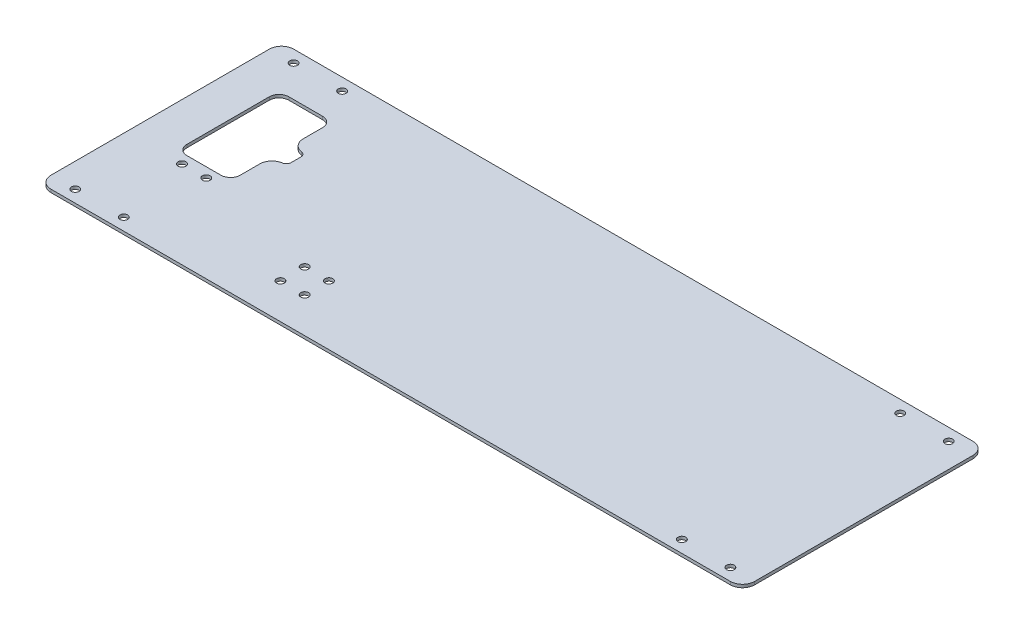
SolidWorks part; units mm, degrees
ref_plane "Front Plane" through (0, 0, 0) normal (0, 0, 1) x (1, 0, 0)
ref_plane "Top Plane" through (0, 0, 0) normal (0, 1, 0) x (1, 0, 0)
ref_plane "Right Plane" through (0, 0, 0) normal (1, 0, 0) x (0, 0, -1)
sketch "Sketch1" plane through (0, 0, 0) normal (0, 1, 0) x (1, 0, 0)
  line L0 (128.27, 0) -> (-128.27, 0) construction
  line L1 (184.15, 63.5) -> (-184.15, 63.5)
  line L2 (184.15, 63.5) -> (184.15, -63.5)
  line L3 (184.15, -63.5) -> (-184.15, -63.5)
  line L4 (-184.15, 63.5) -> (-184.15, -63.5)
  line L5 (184.15, 63.5) -> (-184.15, -63.5) construction
  line L6 (184.15, -63.5) -> (-184.15, 63.5) construction
  line L7 (-128.27, 0) -> (-128.27, 31.75) construction
  line L8 (-128.27, 31.75) -> (-134.62, 31.75) construction
  line L9 (-128.27, -6.35) -> (-134.62, -6.35) construction
  line L12 (-162.56, -12.7) -> (-162.56, 40.64)
  line L15 (-134.62, -12.7) -> (-162.56, -12.7)
  line L17 (-134.62, 40.64) -> (-162.56, 40.64)
  line L18 (0, 63.5) -> (0, -63.5) construction
  line L19 (-134.62, 40.64) -> (-134.62, -12.7)
  line L20 (-162.56, 31.75) -> (-168.91, 31.75) construction
  line L21 (-76.2, -45.0215) -> (-76.2, -32.3215) construction
  line L22 (-63.5, -45.0215) -> (-76.2, -45.0215) construction
  line L23 (-162.56, -3.81) -> (-168.91, -3.81) construction
  line L25 (128.27, 31.75) -> (128.27, -6.35) construction
  line L26 (-76.2, -32.3215) -> (-63.5, -32.3215) construction
  line L30 (-63.5, -32.3215) -> (-63.5, -45.0215) construction
  line L31 (184.15, -17.78) -> (154.94, -17.78) construction
  line L32 (146.05, 57.15) -> (184.15, 57.15) construction
  line L33 (154.94, -17.78) -> (142.24, -17.78) construction
  line L34 (146.05, -57.15) -> (184.15, -57.15) construction
  line L35 (-146.05, -57.15) -> (-184.15, -57.15) construction
  line L36 (-146.05, 57.15) -> (-184.15, 57.15) construction
  line L37 (-128.27, 0) -> (-128.27, -6.35) construction
  line L38 (-184.15, -17.78) -> (-154.94, -17.78) construction
  line L39 (-154.94, -17.78) -> (-142.24, -17.78) construction
  line L40 (-134.62, 19.05) -> (-127, 19.05)
  line L41 (-127, 19.05) -> (-127, 8.89)
  line L42 (-127, 8.89) -> (-134.62, 8.89)
  circle A0 centre (-128.27, 31.75) radius 2.032 construction
  circle A1 centre (-128.27, -6.35) radius 2.032 construction
  circle A2 centre (-168.91, 31.75) radius 2.032 construction
  circle A3 centre (-168.91, -3.81) radius 2.032 construction
  circle A4 centre (168.91, 31.75) radius 2.032 construction
  circle A5 centre (128.27, 31.75) radius 2.032 construction
  circle A6 centre (128.27, -6.35) radius 2.032 construction
  circle A7 centre (168.91, -3.81) radius 2.032 construction
  circle A8 centre (171.45, -57.15) radius 2.032
  circle A9 centre (146.05, -57.15) radius 2.032
  circle A10 centre (171.45, 57.15) radius 2.032
  circle A11 centre (146.05, 57.15) radius 2.032
  circle A12 centre (-146.05, -57.15) radius 2.032
  circle A13 centre (-171.45, -57.15) radius 2.032
  circle A14 centre (-146.05, 57.15) radius 2.032
  circle A15 centre (-171.45, 57.15) radius 2.032
  circle A16 centre (142.24, -17.78) radius 2.032 construction
  circle A17 centre (154.94, -17.78) radius 2.032 construction
  circle A18 centre (-154.94, -17.78) radius 2.032
  circle A19 centre (-142.24, -17.78) radius 2.032
  circle A20 centre (-76.2, -45.0215) radius 2.032
  circle A21 centre (-63.5, -45.0215) radius 2.032
  circle A22 centre (-76.2, -32.3215) radius 2.032
  circle A23 centre (-63.5, -32.3215) radius 2.032
  point P0 (0, 0)
  point P11 (-128.27, 0)
  point P13 (-134.62, 31.75)
  point P17 (-134.62, -6.35)
  point P37 (0, 0)
  point P50 (171.45, 57.15)
  point P51 (146.05, 57.15)
  point P56 (171.45, -57.15)
  point P57 (146.05, -57.15)
  point P84 (-130.81, 19.05)
  point P87 (130.81, 19.05)
  dimension "D5" = 4.064
  dimension "D6" = 8.89
  dimension "D18" = 4.064
  dimension "D1" = 368.3
  dimension "D2" = 127
  dimension "D3" = 128.27
  dimension "D4" = 38.1
  dimension "D7" = 6.35
  dimension "D8" = 27.94
  dimension "D9" = 53.34
  dimension "D10" = 8.89
  dimension "D11" = 6.35
  dimension "D12" = 8.89
  dimension "D13" = 15.24
  dimension "D14" = 12.7
  dimension "D15" = 38.1
  dimension "D16" = 12.7
  dimension "D17" = 38.1
  dimension "D19" = 31.75
  dimension "D20" = 6.35
  dimension "D21" = 6.35
  dimension "D22" = 5.08
  dimension "D23" = 29.21
  dimension "D24" = 12.7
  dimension "D25" = 107.95
  dimension "D26" = 12.7
  dimension "D27" = 7.62
  dimension "D28" = 10.16
  dimension "D29" = 21.59
  dimension "D30" = 18.4785
  dimension "D31" = 12.7
extrude "Boss-Extrude1" add sketch "Sketch1" along normal blind 1.5875 contours L1 L4 L3 L2 A18 A17 A16 A14 A12 A11 A10 A9 A8 L41 L42 L19 L15 L12 L17 L40 A13 A15 A19 region at (5.3094, 0, 0.4316)
sketch "Sketch2" [suppressed] plane through (0, 1.5875, 0) normal (0, 1, 0) x (1, 0, 0)
  line L0 (-69.85, 63.5) -> (-69.85, -63.5)
  line L1 (184.15, 63.5) -> (-184.15, 63.5) construction
  line L2 (184.15, -63.5) -> (-184.15, -63.5) construction
  circle A0 centre (-82.55, -45.0215) radius 2.032 construction
  circle M9 centre (146.05, 57.15) radius 2.032
  circle M10 centre (171.45, 57.15) radius 2.032
  circle M11 centre (146.05, -57.15) radius 2.032
  circle M12 centre (171.45, -57.15) radius 2.032
  line M13 (184.15, 63.5) -> (-184.15, 63.5)
  line M15 (-184.15, -63.5) -> (184.15, -63.5)
  line M16 (184.15, -63.5) -> (184.15, 63.5)
  dimension "D1" = 12.7
extrude "Cut-Extrude1" [suppressed] cut sketch "Sketch2" against normal through all flip side to cut contours L0 M13 M15 M16 M10 M12 M11 M9
fillet "Fillet1" radius 5.08 4 edges at (-134.62, 0.7937, 12.7) (-162.56, 0.7937, 12.7) (-162.56, 0.7937, -40.64) (-134.62, 0.7937, -40.64)
fillet "Fillet3" radius 6.35 4 edges at (184.15, 0.7937, 63.5) (184.15, 0.7937, -63.5) (-184.15, 0.7937, 63.5) (-184.15, 0.7937, -63.5)
fillet "Fillet4" radius 2.54 2 edges at (-127, 0.7937, -8.89) (-127, 0.7937, -19.05)
fillet "Fillet5" radius 6.35 2 edges at (-134.62, 0.7937, -8.89) (-134.62, 0.7937, -19.05)
fillet "Fillet6" [suppressed] radius 6.35
